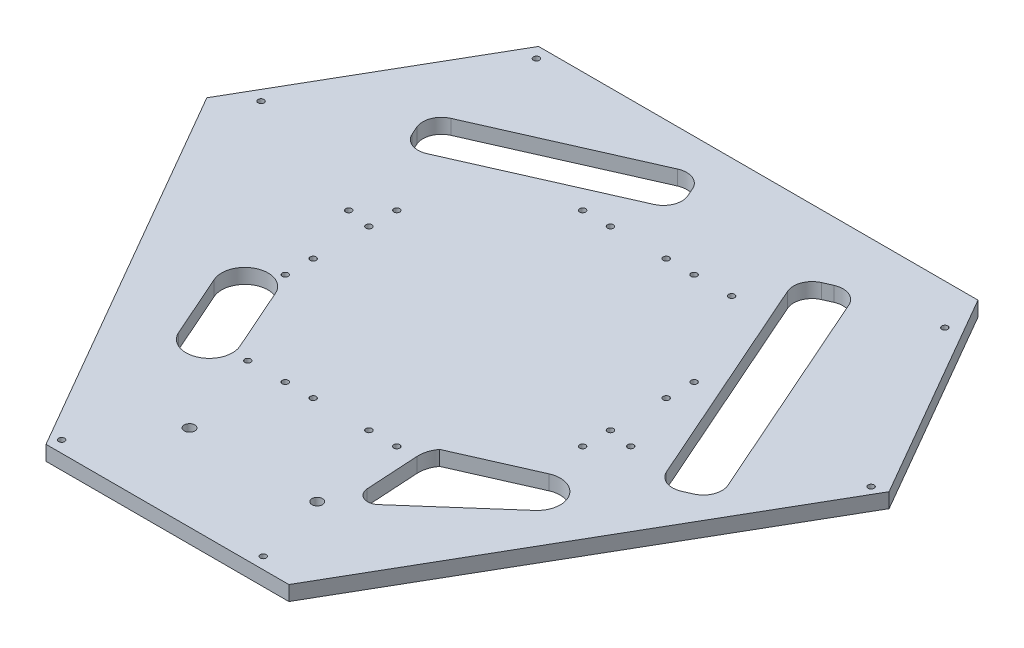
SolidWorks part; units mm, degrees
material "Pin"
ref_plane "Plan de face" through (0, 0, 0) normal (0, 0, 1) x (1, 0, 0)
ref_plane "Plan de dessus" through (0, 0, 0) normal (0, 1, 0) x (1, 0, 0)
ref_plane "Plan de droite" through (0, 0, 0) normal (1, 0, 0) x (0, 0, -1)
sketch "BB_position" plane through (0, 0, 0) normal (0, 1, 0) x (1, 0, 0)
  line L0 (-112.5, 64.9519) -> (112.5, 64.9519) construction
  line L7 (112.5, 64.9519) -> (0, -129.9038) construction
  line L8 (0, -129.9038) -> (-112.5, 64.9519) construction
  circle A0 centre (0, 0) radius 129.9038 construction
  circle A1 centre (-112.5, 64.9519) radius 5 construction
  circle A2 centre (112.5, 64.9519) radius 5 construction
  circle A3 centre (0, -129.9038) radius 5 construction
  dimension "D1" = 225
  dimension "D2" = 10
sketch "BB_Footprint" plane through (0, 0, 0) normal (0, 1, 0) x (1, 0, 0)
  line L0 (-112.5, 64.9519) -> (-130.615, 33.5758) construction
  line L1 (-130.615, 33.5758) -> (-133.9232, 35.4858) construction
  line L2 (-133.9232, 35.4858) -> (-90.5354, 110.6358) construction
  line L3 (97.6932, 98.238) -> (141.0811, 23.088) construction
  line L4 (112.5, 64.9519) -> (94.385, 96.328) construction
  line L5 (94.385, 96.328) -> (97.6932, 98.238) construction
  line L6 (36.23, -133.7238) -> (-50.5457, -133.7238) construction
  line L7 (0, -129.9038) -> (36.23, -129.9038) construction
  line L8 (36.23, -129.9038) -> (36.23, -133.7238) construction
  circle A0 centre (-112.5, 64.9519) radius 5 construction
  circle A1 centre (0, 0) radius 129.9038 construction
  circle A2 centre (-112.5, 64.9519) radius 5 construction
  circle A3 centre (112.5, 64.9519) radius 5 construction
  circle A4 centre (0, -129.9038) radius 5 construction
  point P2 (0, 0)
  point P6 (0, -129.9038)
  point P23 (0, 0)
  dimension "D1" = 3.82
  dimension "D2" = 36.23
  dimension "D3" = 86.7757
  dimension "D4" = 3
sketch "Esquisse3" plane through (0, 0, 0) normal (0, 1, 0) x (1, 0, 0)
  line L0 (-94.5768, 115.6358) -> (94.5768, 115.6358)
  line L1 (-94.5768, 115.6358) -> (-146.8546, 25.088)
  line L2 (-146.8546, 25.088) -> (-52.2778, -138.7238)
  line L3 (-52.2778, -138.7238) -> (52.2778, -138.7238)
  line L4 (52.2778, -138.7238) -> (146.8546, 25.088)
  line L5 (146.8546, 25.088) -> (94.5768, 115.6358)
  line L6 (-133.9232, 35.4858) -> (-90.5354, 110.6358) construction
  point P2 (0, 115.6358)
  point P7 (0, -138.7238)
  point P9 (106.0676, 115.6358)
  point P12 (50.0532, -142.5769)
  dimension "D1" = 5
  dimension "D2" = 4
  dimension "D3" = 5
sketch "TB_boltPattern" plane through (0, 0, 0) normal (0, 1, 0) x (1, 0, 0)
  line L0 (0, 143.3581) -> (0, -141.7362) construction
  line L1 (-23, 57.7) -> (-13, 57.7) construction
  line L2 (-23, 57.7) -> (-23, 43.7) construction
  line L3 (-23, 43.7) -> (-13, 43.7) construction
  line L4 (-13, 57.7) -> (-13, 43.7) construction
  line L5 (-57.7, 23) -> (-43.7, 23) construction
  line L6 (-57.7, 23) -> (-57.7, 13) construction
  line L7 (-57.7, 13) -> (-43.7, 13) construction
  line L8 (-43.7, 23) -> (-43.7, 13) construction
  line L9 (-204.4729, 0) -> (279.6048, 0) construction
  circle A0 centre (-24, 64) radius 1.6 construction
  circle A1 centre (-12, 64) radius 1.6 construction
  circle A2 centre (-64, 24) radius 1.6 construction
  circle A3 centre (-64, 12) radius 1.6 construction
  point P8 (-18, 57.7)
  dimension "D5" = 3.2
  dimension "D10" = 6.3
  dimension "D1" = 12
  dimension "D2" = 12
  dimension "D3" = 40
  dimension "D4" = 40
  dimension "D6" = 14
  dimension "D7" = 10
  dimension "D8" = 1
  dimension "D9" = 6.3
  dimension "D11" = 1
  dimension "D12" = 12
  dimension "D13" = 12
extrude "Plate" add sketch "Esquisse3" against normal blind 6.35
hole_wizard "BBCase_boltPattern" positions "Esquisse6" profile "Esquisse8" hole size "M3" standard "Ansi Metric"
sketch "Esquisse6" plane through (0, 0, 0) normal (0, 1, 0) x (1, 0, 0)
  point P0 (-90.5354, 110.6358)
  point P3 (-133.9232, 35.4858)
sketch "Esquisse8" plane through (-90.5354, 0, -110.6358) normal (1, 0, 0) x (0, 0, 1)
  line L0 (0, 0) -> (0, 7.1311)
  line L1 (0, 7.1311) -> (1.3, 6.35)
  line L2 (1.3, 6.35) -> (1.3, 0)
  line L5 (1.3, 0) -> (0, 0)
  line L10 (0, 7.1311) -> (-1.3, 6.35) construction
  line L11 (0, -6.35) -> (0, 107.95) construction
  dimension "Diamètre du perçage" = 2.6
  dimension "Profondeur du perçage" = 6.35
  dimension "Angle de pointe" = 118
ref_axis "Axe1" through (0, 0, 0) along (0, 1, 0)
pattern_circular "Répétition circulaire1" count 3 over 360 about axis through (0, 0, 0) along (0, 1, 0) of "BBCase_boltPattern"
hole_wizard "Dégagement M32" positions "Esquisse9" profile "Esquisse10" hole size "M3" standard "Ansi Metric"
sketch "Esquisse9" plane through (0, 0, 0) normal (0, 1, 0) x (1, 0, 0)
  point P0 (-24, 64)
  point P3 (-12, 64)
  point P6 (-64, 24)
  point P9 (-64, 12)
sketch "Esquisse10" plane through (-24, 0, -64) normal (1, 0, 0) x (0, 0, 1)
  line L0 (0, 0) -> (0, 7.1311)
  line L1 (0, 7.1311) -> (1.3, 6.35)
  line L2 (1.3, 6.35) -> (1.3, 0)
  line L5 (1.3, 0) -> (0, 0)
  line L10 (0, 7.1311) -> (-1.3, 6.35) construction
  line L11 (0, -6.35) -> (0, 107.95) construction
  dimension "Diamètre du perçage" = 2.6
  dimension "Profondeur du perçage" = 6.35
  dimension "Angle de pointe" = 118
pattern_circular "Répétition circulaire2" count 4 over 360 about axis through (0, 0, 0) along (0, 1, 0) of "Dégagement M32"
sketch "HB_Footprint" plane through (0, 0, 0) normal (0, 1, 0) x (1, 0, 0)
  line L0 (-74.3426, 13.6262) -> (40.0015, 64.1278) construction
  line L1 (40.0015, 64.1278) -> (74.3426, -13.6262) construction
  line L2 (-74.3426, 13.6262) -> (-40.0015, -64.1278) construction
  line L3 (-40.0015, -64.1278) -> (74.3426, -13.6262) construction
  line L8 (-77.8072, 30.1336) -> (-30.1336, -77.8072) construction
  line L9 (-30.1336, -77.8072) -> (77.8072, -30.1336) construction
  line L10 (77.8072, -30.1336) -> (30.1336, 77.8072) construction
  line L11 (-77.8072, 30.1336) -> (30.1336, 77.8072) construction
  line L12 (-23.8368, 53.9704) -> (23.8368, -53.9704) construction
  line L13 (-57.1721, -25.2508) -> (0, 0) construction
  circle A0 centre (-74.3426, 13.6262) radius 1.6 construction
  circle A1 centre (40.0015, 64.1278) radius 1.6 construction
  circle A2 centre (-40.0015, -64.1278) radius 1.6 construction
  circle A3 centre (74.3426, -13.6262) radius 1.6 construction
  point P10 (23.8368, -53.9704)
  point P19 (-17.1706, 38.877)
  dimension "D4" = 3.2
  dimension "D1" = 125
  dimension "D2" = 85
  dimension "D3" = 118
hole_wizard "Dégagement M33" positions "Esquisse11" profile "Esquisse12" hole size "M3" standard "Ansi Metric"
sketch "Esquisse11" plane through (0, 0, 0) normal (0, 1, 0) x (1, 0, 0)
  point P0 (-74.3426, 13.6262)
  point P3 (-40.0015, -64.1278)
  point P6 (74.3426, -13.6262)
  point P9 (40.0015, 64.1278)
sketch "Esquisse12" plane through (-74.3426, 0, -13.6262) normal (1, 0, 0) x (0, 0, 1)
  line L0 (0, 0) -> (0, 7.1311)
  line L1 (0, 7.1311) -> (1.3, 6.35)
  line L2 (1.3, 6.35) -> (1.3, 0)
  line L5 (1.3, 0) -> (0, 0)
  line L10 (0, 7.1311) -> (-1.3, 6.35) construction
  line L11 (0, -6.35) -> (0, 107.95) construction
  dimension "Diamètre du perçage" = 2.6
  dimension "Profondeur du perçage" = 6.35
  dimension "Angle de pointe" = 118
sketch "Esquisse13" plane through (0, 0, 0) normal (0, 1, 0) x (1, 0, 0)
  line L0 (113.0252, -14.5791) -> (94.7302, -22.6594)
  line L1 (94.7302, -22.6594) -> (47.0566, 85.2815)
  line L2 (47.0566, 85.2815) -> (65.3516, 93.3617)
  line L3 (65.3516, 93.3617) -> (113.0252, -14.5791)
  line L5 (-77.8072, 30.1336) -> (30.1336, 77.8072) construction
  line L7 (40.0015, 64.1278) -> (74.3426, -13.6262) construction
  line L13 (-30.1336, -77.8072) -> (77.8072, -30.1336) construction
  line L14 (-11.64, 103.085) -> (-93.9678, 66.7238)
  line L15 (-93.9678, 66.7238) -> (-85.8875, 48.4287)
  line L16 (-85.8875, 48.4287) -> (-3.5597, 84.7899)
  line L17 (-3.5597, 84.7899) -> (-11.64, 103.085)
  line L18 (-77.8072, 30.1336) -> (-30.1336, -77.8072) construction
  dimension "D1" = 15
  dimension "D2" = 20
  dimension "D5" = 20
  dimension "D6" = 90
  dimension "D7" = 20
extrude "Enlèv. mat.-Extru.1" cut sketch "Esquisse13" against normal up to surface (6.35 mm away) up to face at (-40.0015, -6.35, 65.4278)
sketch "Esquisse15" plane through (0, 0, 0) normal (0, 1, 0) x (1, 0, 0)
  line L0 (-27.48, -101.7238) -> (27.48, -101.7238) construction
  line L1 (0, 200143.3581) -> (0, -200141.7362) construction
  line L2 (-52.2778, -138.7238) -> (52.2778, -138.7238) construction
  circle A0 centre (-27.48, -101.7238) radius 3.5746 construction
  circle A1 centre (27.48, -101.7238) radius 3.5746 construction
  point P4 (0, -101.7238)
  dimension "D1" = 54.96
  dimension "D2" = 37
hole_wizard "Dégagement M51" positions "Esquisse16" profile "Esquisse17" hole size "M5" standard "Ansi Metric"
sketch "Esquisse16" plane through (0, 0, 0) normal (0, 1, 0) x (1, 0, 0)
  point P0 (-27.48, -101.7238)
  point P3 (27.48, -101.7238)
sketch "Esquisse17" plane through (-27.48, 0, 101.7238) normal (1, 0, 0) x (0, 0, 1)
  line L0 (0, 0) -> (0, 7.714)
  line L1 (0, 7.714) -> (2.27, 6.35)
  line L2 (2.27, 6.35) -> (2.27, 0)
  line L5 (2.27, 0) -> (0, 0)
  line L10 (0, 7.714) -> (-2.27, 6.35) construction
  line L11 (0, -6.35) -> (0, 107.95) construction
  dimension "Diamètre du perçage" = 4.54
  dimension "Profondeur du perçage" = 6.35
  dimension "Angle de pointe" = 118
sketch "Esquisse18" plane through (0, 0, 0) normal (0, 1, 0) x (1, 0, 0)
  line L0 (71.0075, -50.6279) -> (43.5649, -62.7483) construction
  line L2 (66.9674, -41.4803) -> (34.336, -55.8925)
  line L3 (-30.1336, -77.8072) -> (77.8072, -30.1336) construction
  line L4 (23.8368, -53.9704) -> (77.8072, -30.1336) construction
  line L5 (50.822, -42.052) -> (57.2862, -56.6881) construction
  line L6 (-68.3683, -37.0282) -> (-56.2479, -64.4708) construction
  line L7 (-59.2207, -32.9881) -> (-47.1003, -60.4307)
  line L8 (-77.5158, -41.0684) -> (-65.3954, -68.511)
  line L9 (-74.3426, 13.6262) -> (-40.0015, -64.1278) construction
  line L10 (-57.1721, -25.2508) -> (-40.0015, -64.1278) construction
  line L11 (-48.5868, -44.6893) -> (-62.3081, -50.7495) construction
  line L12 (32.0883, -63.4284) -> (33.4385, -86.2128)
  line L13 (41.7305, -89.6726) -> (77.6091, -58.1391)
  arc A0 (77.6091, -58.1391) -> (66.9674, -41.4803) centre (71.0075, -50.6279) ccw
  arc A1 (34.336, -55.8925) -> (32.0883, -63.4284) centre (43.5649, -62.7483) ccw
  arc A2 (-59.2207, -32.9881) -> (-77.5158, -41.0684) centre (-68.3683, -37.0282) ccw
  arc A3 (-65.3954, -68.511) -> (-47.1003, -60.4307) centre (-56.2479, -64.4708) ccw
  arc A4 (33.4385, -86.2128) -> (41.7305, -89.6726) centre (38.4297, -85.917) ccw
  point P2 (57.2862, -56.6881)
  point P16 (-62.3081, -50.7495)
  point P35 (34.0438, -96.4284)
  dimension "D4" = 15
  dimension "D6" = 10
  dimension "D1" = 10
  dimension "D11" = 5
  dimension "D2" = 6
  dimension "D3" = 30
  dimension "D5" = 30
  dimension "D7" = 35
  dimension "D8" = 58
  dimension "D9" = 10
  dimension "D10" = 33
extrude "Enlèv. mat.-Extru.3" cut sketch "Esquisse18" against normal up to surface (6.35 mm away) up to face at (-27.48, -6.35, 103.9938)
fillet "Congé1" radius 8 8 edges at (47.0566, -3.175, -85.2815) (65.3516, -3.175, -93.3617) (113.0252, -3.175, 14.5791) (94.7302, -3.175, 22.6594) (-11.64, -3.175, -103.085) (-3.5597, -3.175, -84.7899) (-85.8875, -3.175, -48.4287) (-93.9678, -3.175, -66.7238)
